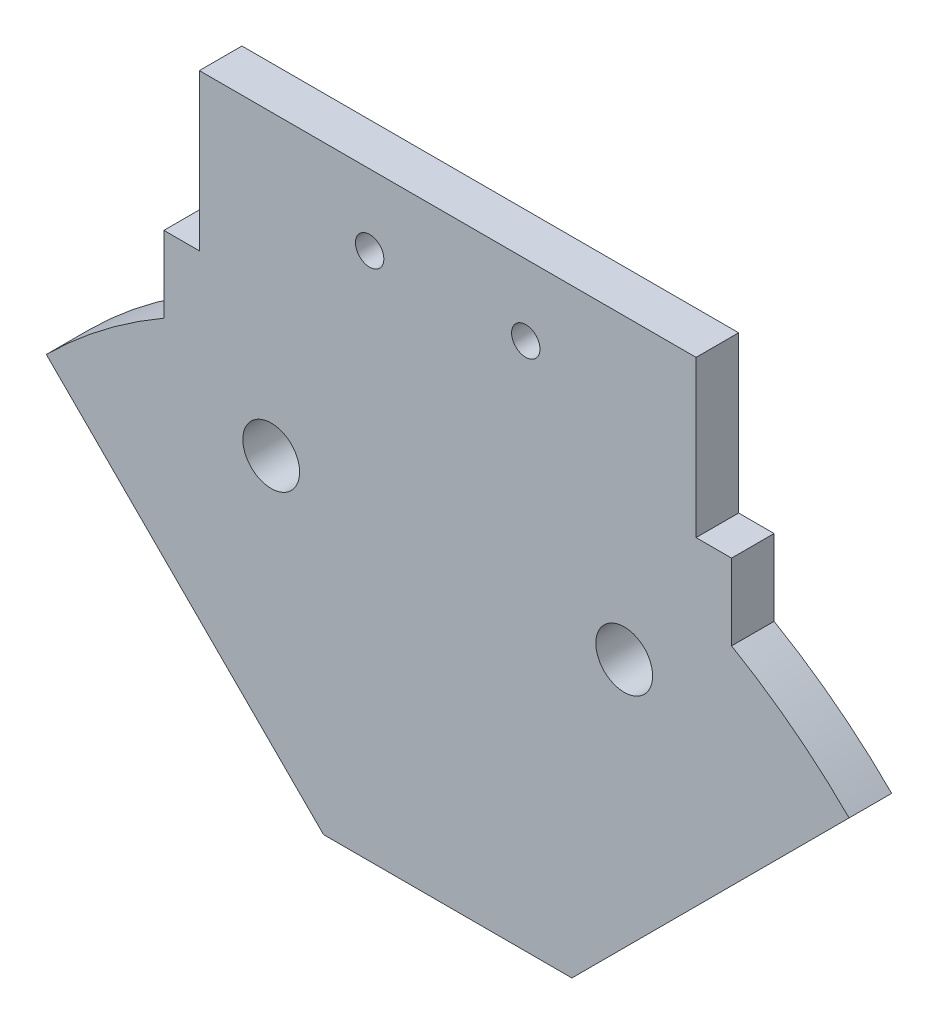
SolidWorks part; units mm, degrees
material "Plain Carbon Steel"
ref_plane "Front Plane" through (0, 0, 0) normal (0, 0, 1) x (1, 0, 0)
ref_plane "Top Plane" through (0, 0, 0) normal (0, 1, 0) x (1, 0, 0)
ref_plane "Right Plane" through (0, 0, 0) normal (1, 0, 0) x (0, 0, -1)
sketch "Sketch1" plane through (0, 0, 0) normal (0, 0, 1) x (1, 0, 0)
  line L0 (0, -55) -> (0, 55) construction
  line L3 (-80, 0) -> (-17.5, 0)
  line L5 (-60.0522, 24.8744) -> (0, 0) construction
  line L6 (0, 0) -> (60.0522, 24.8744) construction
  line L7 (55, 0) -> (-55, 0) construction
  line L8 (17.5, 0) -> (80, 0)
  line L9 (24.8744, 60.0522) -> (0, 0) construction
  arc A0 (17.5, 0) -> (-17.5, 0) centre (0, 0) ccw
  circle A1 centre (24.8744, 60.0522) radius 4
  circle A12 centre (60.0522, 24.8744) radius 4
  arc A15 (80, 0) -> (-80, 0) centre (0, 0) ccw
  circle A17 centre (-60.0522, 24.8744) radius 4
  circle A18 centre (-24.8744, 60.0522) radius 4
  point P0 (0, 0)
  point P26 (0, -19.4444)
  point P27 (0, 0)
  point P29 (0, 0)
  dimension "D1" = 22.5
  dimension "D4" = 8
  dimension "D7" = 80
  dimension "D8" = 35
  dimension "D2" = 22.5
  dimension "D3" = 65
  dimension "D5" = 65
  dimension "D6" = 65
  dimension "D9" = 22.5
extrude "Boss-Extrude1" add sketch "Sketch1" along normal blind 6
sketch "Sketch2" plane through (0, 0, 0) normal (0, 0, 1) x (1, 0, 0)
  line L0 (-12.3744, 12.3744) -> (-56.5685, 56.5685)
  line L1 (-56.5685, 56.5685) -> (-80, 56.5685)
  line L2 (-80, 56.5685) -> (-80, 0)
  line L3 (-80, 0) -> (-17.5, 0)
  line L4 (80, 0) -> (80, 56.5685)
  line L5 (80, 56.5685) -> (56.5685, 56.5685)
  line L6 (56.5685, 56.5685) -> (12.3744, 12.3744)
  line L7 (55, 0) -> (-55, 0) construction
  line L8 (17.5, 0) -> (80, 0)
  arc A0 (80, 0) -> (-80, 0) centre (0, 0) ccw construction
  arc A1 (17.5, 0) -> (12.3744, 12.3744) centre (0, 0) ccw
  arc A2 (-12.3744, 12.3744) -> (-17.5, 0) centre (0, 0) ccw
  dimension "D1" = 17.5
extrude "Cut-Extrude1" cut sketch "Sketch2" along normal through all
sketch "Sketch3" plane through (0, 0, 0) normal (0, 0, 1) x (1, 0, 0)
  line L0 (0, -55) -> (0, 55) construction
  line L1 (-40, 69.282) -> (40, 69.282)
  line L2 (-40, 69.282) -> (-40, 80)
  line L3 (-40, 80) -> (40, 80)
  line L4 (40, 69.282) -> (40, 80)
  line L5 (-40, 69.282) -> (40, 80) construction
  line L6 (-40, 80) -> (40, 69.282) construction
  arc A0 (56.5685, 56.5685) -> (-56.5685, 56.5685) centre (0, 0) ccw construction
  point P0 (0, 74.641)
  point P5 (0, 80)
  dimension "D1" = 80
extrude "Boss-Extrude2" add sketch "Sketch3" along normal blind 6
sketch "Sketch4" plane through (0, 0, 0) normal (0, 0, 1) x (1, 0, 0)
  line L0 (-12.3744, 12.3744) -> (-56.5685, 56.5685) construction
  line L1 (-17.5, 17.5) -> (17.5, 17.5)
  line L2 (-17.5, 17.5) -> (-17.5, 12.3744)
  line L3 (-17.5, 12.3744) -> (17.5, 12.3744)
  line L4 (17.5, 17.5) -> (17.5, 12.3744)
  line L5 (56.5685, 56.5685) -> (12.3744, 12.3744) construction
  arc A0 (12.3744, 12.3744) -> (-12.3744, 12.3744) centre (0, 0) ccw construction
extrude "Cut-Extrude2" cut sketch "Sketch4" along normal through all
sketch "Sketch5" plane through (0, 80, 0) normal (0, 1, 0) x (1, 0, 0)
  line L0 (40, -6) -> (-40, -6) construction
  line L1 (-35, 0) -> (35, 0)
  line L2 (-35, 0) -> (-35, -6)
  line L3 (-35, -6) -> (35, -6)
  line L4 (35, 0) -> (35, -6)
  line L5 (-40, -6) -> (-40, 0) construction
  line L6 (40, -6) -> (40, 0) construction
  line L7 (40, 0) -> (-40, 0) construction
  dimension "D1" = 5
  dimension "D2" = 5
extrude "Boss-Extrude3" add sketch "Sketch5" along normal blind 22
sketch "Sketch6" plane through (0, 0, 0) normal (0, 0, -1) x (-1, 0, 0)
  line L0 (0, 3.3) -> (0, -3.3) construction
  line L1 (-35, 102) -> (35, 102) construction
  circle A0 centre (11, 92) radius 2
  circle A1 centre (-11, 92) radius 2
  point P4 (0, 0)
  dimension "D1" = 4
  dimension "D2" = 11
  dimension "D3" = 10
extrude "Cut-Extrude3" cut sketch "Sketch6" against normal up to next
